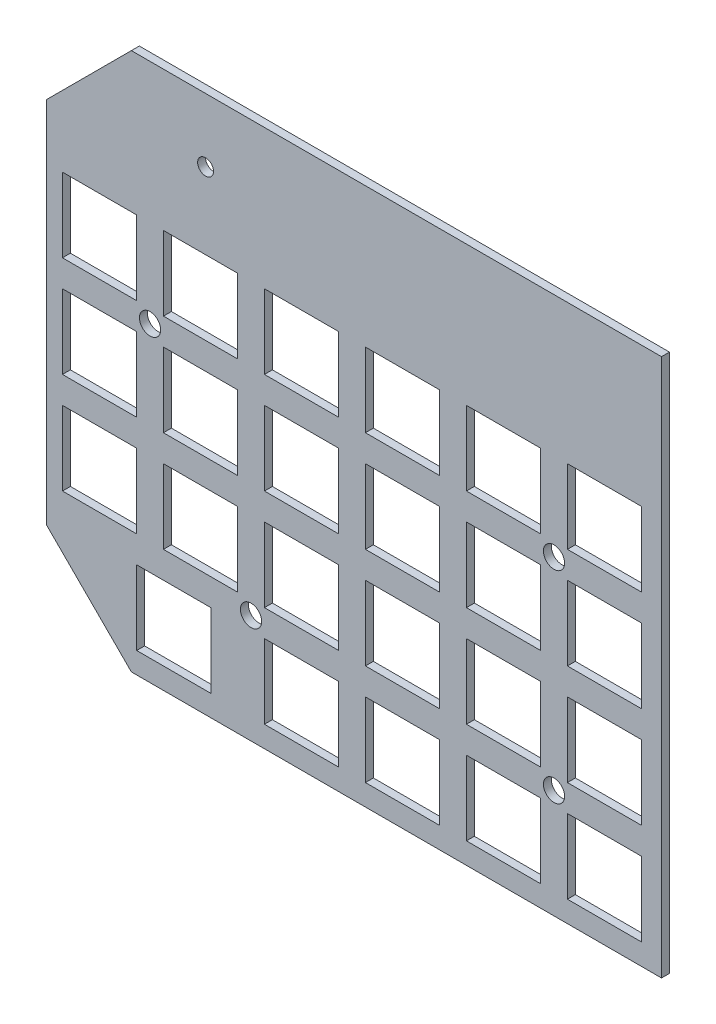
SolidWorks part; units mm, degrees
ref_plane "Plan de face" through (0, 0, 0) normal (0, 0, 1) x (1, 0, 0)
ref_plane "Plan de dessus" through (0, 0, 0) normal (0, 1, 0) x (1, 0, 0)
ref_plane "Plan de droite" through (0, 0, 0) normal (1, 0, 0) x (0, 0, -1)
sketch "Esquisse1" plane through (0, 0, 0) normal (0, 0, 1) x (1, 0, 0)
  line L0 (0, -85) -> (16, -101)
  line L4 (116, 0.5) -> (116, -101)
  line L5 (16, 0.5) -> (0, -15.5)
  line L7 (116, 0.5) -> (16, 0.5)
  line L8 (0, -15.5) -> (0, -85)
  line L9 (16, -101) -> (116, -101)
  dimension "D1" = 101.5
  dimension "D2" = 116
  dimension "D3" = 16
  dimension "D4" = 16
  dimension "D5" = 16
  dimension "D6" = 16
extrude "Boss.-Extru.1" add sketch "Esquisse1" along normal blind 1.5
sketch "Esquisse2" plane through (0, 0, 1.5) normal (0, 0, 1) x (1, 0, 0)
  line L0 (0, -15.5) -> (0, -85) construction
  line L1 (3, -25.85) -> (17, -25.85)
  line L2 (3, -25.85) -> (3, -39.85)
  line L3 (3, -39.85) -> (17, -39.85)
  line L4 (17, -25.85) -> (17, -39.85)
  line L5 (10, -39.85) -> (10, -25.85) construction
  line L6 (3, -32.85) -> (17, -32.85) construction
  line L7 (116, 0.5) -> (16, 0.5) construction
  line L12 (22.05, -25.85) -> (22.05, -39.85)
  line L13 (22.05, -25.85) -> (36.05, -25.85)
  line L14 (36.05, -25.85) -> (36.05, -39.85)
  line L15 (22.05, -39.85) -> (36.05, -39.85)
  line L16 (41.1, -25.85) -> (41.1, -39.85)
  line L17 (41.1, -25.85) -> (55.1, -25.85)
  line L18 (55.1, -25.85) -> (55.1, -39.85)
  line L19 (41.1, -39.85) -> (55.1, -39.85)
  line L20 (60.15, -25.85) -> (60.15, -39.85)
  line L21 (60.15, -25.85) -> (74.15, -25.85)
  line L22 (74.15, -25.85) -> (74.15, -39.85)
  line L23 (60.15, -39.85) -> (74.15, -39.85)
  line L24 (79.2, -25.85) -> (79.2, -39.85)
  line L25 (79.2, -25.85) -> (93.2, -25.85)
  line L26 (93.2, -25.85) -> (93.2, -39.85)
  line L27 (79.2, -39.85) -> (93.2, -39.85)
  line L28 (98.25, -25.85) -> (98.25, -39.85)
  line L29 (98.25, -25.85) -> (112.25, -25.85)
  line L30 (112.25, -25.85) -> (112.25, -39.85)
  line L31 (98.25, -39.85) -> (112.25, -39.85)
  line L32 (22.05, -44.9) -> (22.05, -58.9)
  line L33 (22.05, -44.9) -> (36.05, -44.9)
  line L34 (36.05, -44.9) -> (36.05, -58.9)
  line L35 (22.05, -58.9) -> (36.05, -58.9)
  line L36 (41.1, -44.9) -> (41.1, -58.9)
  line L37 (41.1, -44.9) -> (55.1, -44.9)
  line L38 (55.1, -44.9) -> (55.1, -58.9)
  line L39 (41.1, -58.9) -> (55.1, -58.9)
  line L40 (60.15, -44.9) -> (60.15, -58.9)
  line L41 (60.15, -44.9) -> (74.15, -44.9)
  line L42 (74.15, -44.9) -> (74.15, -58.9)
  line L43 (60.15, -58.9) -> (74.15, -58.9)
  line L44 (79.2, -44.9) -> (79.2, -58.9)
  line L45 (79.2, -44.9) -> (93.2, -44.9)
  line L46 (93.2, -44.9) -> (93.2, -58.9)
  line L47 (79.2, -58.9) -> (93.2, -58.9)
  line L48 (98.25, -44.9) -> (98.25, -58.9)
  line L49 (98.25, -44.9) -> (112.25, -44.9)
  line L50 (112.25, -44.9) -> (112.25, -58.9)
  line L51 (98.25, -58.9) -> (112.25, -58.9)
  line L52 (22.05, -63.95) -> (22.05, -77.95)
  line L53 (22.05, -63.95) -> (36.05, -63.95)
  line L54 (36.05, -63.95) -> (36.05, -77.95)
  line L55 (22.05, -77.95) -> (36.05, -77.95)
  line L56 (41.1, -63.95) -> (41.1, -77.95)
  line L57 (41.1, -63.95) -> (55.1, -63.95)
  line L58 (55.1, -63.95) -> (55.1, -77.95)
  line L59 (41.1, -77.95) -> (55.1, -77.95)
  line L60 (60.15, -63.95) -> (60.15, -77.95)
  line L61 (60.15, -63.95) -> (74.15, -63.95)
  line L62 (74.15, -63.95) -> (74.15, -77.95)
  line L63 (60.15, -77.95) -> (74.15, -77.95)
  line L64 (79.2, -63.95) -> (79.2, -77.95)
  line L65 (79.2, -63.95) -> (93.2, -63.95)
  line L66 (93.2, -63.95) -> (93.2, -77.95)
  line L67 (79.2, -77.95) -> (93.2, -77.95)
  line L68 (98.25, -63.95) -> (98.25, -77.95)
  line L69 (98.25, -63.95) -> (112.25, -63.95)
  line L70 (112.25, -63.95) -> (112.25, -77.95)
  line L71 (98.25, -77.95) -> (112.25, -77.95)
  line L72 (3, -44.9) -> (3, -58.9)
  line L73 (3, -44.9) -> (17, -44.9)
  line L74 (17, -44.9) -> (17, -58.9)
  line L75 (3, -58.9) -> (17, -58.9)
  line L76 (3, -63.95) -> (3, -77.95)
  line L77 (3, -63.95) -> (17, -63.95)
  line L78 (17, -63.95) -> (17, -77.95)
  line L79 (3, -77.95) -> (17, -77.95)
  line L112 (41.1, -83) -> (41.1, -97)
  line L113 (41.1, -83) -> (55.1, -83)
  line L114 (55.1, -83) -> (55.1, -97)
  line L115 (41.1, -97) -> (55.1, -97)
  line L116 (60.15, -83) -> (60.15, -97)
  line L117 (60.15, -83) -> (74.15, -83)
  line L118 (74.15, -83) -> (74.15, -97)
  line L119 (60.15, -97) -> (74.15, -97)
  line L120 (79.2, -83) -> (79.2, -97)
  line L121 (79.2, -83) -> (93.2, -83)
  line L122 (93.2, -83) -> (93.2, -97)
  line L123 (79.2, -97) -> (93.2, -97)
  line L124 (98.25, -83) -> (98.25, -97)
  line L125 (98.25, -83) -> (112.25, -83)
  line L126 (112.25, -83) -> (112.25, -97)
  line L127 (98.25, -97) -> (112.25, -97)
  line L128 (3, -83) -> (3, -97) [skipped]
  line L129 (3, -83) -> (17, -83) [skipped]
  line L130 (17, -83) -> (17, -97) [skipped]
  line L131 (3, -97) -> (17, -97) [skipped]
  line L132 (22.05, -83) -> (22.05, -97) [skipped]
  line L133 (22.05, -83) -> (36.05, -83) [skipped]
  line L134 (36.05, -83) -> (36.05, -97) [skipped]
  line L135 (22.05, -97) -> (36.05, -97) [skipped]
  line L137 (17, -83) -> (31, -83)
  line L138 (17, -83) -> (17, -97)
  line L139 (17, -97) -> (31, -97)
  line L140 (31, -83) -> (31, -97)
  line L141 (24, -97) -> (24, -83) construction
  line L142 (17, -90) -> (31, -90) construction
  line L143 (16, -101) -> (116, -101) construction
  line L144 (17, -39.85) -> (22.05, -44.9) construction
  line L146 (93.2, -39.85) -> (98.25, -44.9) construction
  line L147 (93.2, -77.95) -> (98.25, -83) construction
  line L148 (36.05, -77.95) -> (41.1, -83) construction
  circle A4 centre (19.525, -42.375) radius 2
  circle A5 centre (95.725, -42.375) radius 2
  circle A6 centre (95.725, -80.475) radius 2
  circle A7 centre (38.575, -80.475) radius 2
  circle A8 centre (30, -11.5) radius 1.5
  point P0 (10, -32.85)
  point P19 (24, -90)
  dimension "D5" = 4
  dimension "D7" = 12
  dimension "D6" = 30
  dimension "D1" = 14
  dimension "D2" = 14
  dimension "D3" = 3
  dimension "D4" = 6
  dimension "D9" = 14
  dimension "D10" = 14
  dimension "D11" = 17
  dimension "D8" = 4
extrude "Enlèv. mat.-Extru.1" cut sketch "Esquisse2" against normal blind 1.5
